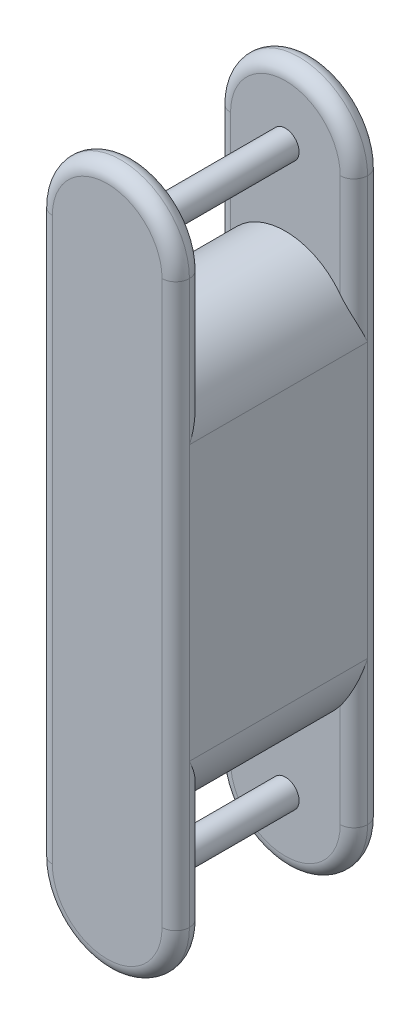
SolidWorks part; units mm, degrees
ref_plane "Front Plane" through (0, 0, 0) normal (0, 0, 1) x (1, 0, 0)
ref_plane "Top Plane" through (0, 0, 0) normal (0, 1, 0) x (1, 0, 0)
ref_plane "Right Plane" through (0, 0, 0) normal (1, 0, 0) x (0, 0, -1)
sketch "Sketch3" plane through (0, 0, 0) normal (0, 0, 1) x (1, 0, 0)
  line L0 (-50, -150) -> (-50, -205)
  line L1 (-50, 150) -> (50, 150)
  line L2 (-50, 150) -> (-50, -150)
  line L3 (-50, -150) -> (50, -150)
  line L4 (50, 150) -> (50, -150)
  line L5 (-50, 150) -> (50, -150) construction
  line L6 (-50, -150) -> (50, 150) construction
  line L7 (50, -150) -> (50, -205)
  line L8 (-50, 150) -> (-50, 205)
  line L9 (50, 150) -> (50, 205)
  arc A0 (-50, -205) -> (50, -205) centre (0, -205) ccw
  arc A1 (-50, 205) -> (50, 205) centre (0, 205) cw
  point P0 (0, 0)
  dimension "D1" = 300
  dimension "D2" = 100
  dimension "D3" = 55
  dimension "D4" = 55
  dimension "D5" = 55
  dimension "D6" = 55
extrude "Boss-Extrude1" add sketch "Sketch3" along normal mid plane 150 contours L4 L1 L2 L3 | L0 A0 L7 L3 | A1 L8 L1 L9 | L2 L1 L4 L3 region at (0, -197.7955, 0) region at (0, 0, 0) region at (0, 197.7955, 0)
sketch "Sketch4" plane through (0, 0, 0) normal (0, 1, 0) x (1, 0, 0)
  line L1 (-50, 55) -> (50, 55)
  line L2 (-50, 55) -> (-50, -55)
  line L3 (-50, -55) -> (50, -55)
  line L4 (50, 55) -> (50, -55)
  line L5 (-50, 55) -> (50, -55) construction
  line L6 (-50, -55) -> (50, 55) construction
  point P0 (0, 0)
  dimension "D1" = 100
  dimension "D2" = 110
extrude "Cut-Extrude1" cut sketch "Sketch4" against normal up to surface (55 mm away) from offset 150 up to face at (0, -230, 0) offset against normal yes
sketch "Sketch6" plane through (0, 0, 0) normal (0, 0, 1) x (1, 0, 0)
  arc A0 (-50, -205) -> (50, -205) centre (0, -205) ccw construction
  arc A1 (-50, -205) -> (50, -205) centre (0, -205) ccw
  circle A2 centre (0, -205) radius 10
  dimension "D1" = 20
extrude "Boss-Extrude2" add sketch "Sketch6" along normal mid plane 110 contours A2 region at (0, -205, 0)
extrude "Cut-Extrude2" cut sketch "Sketch4<2>" along normal up to surface (55 mm away) from offset 150 up to face at (0, 230, 0)
sketch "Sketch4<2>" plane through (0, 0, 0) normal (0, 1, 0) x (1, 0, 0) same geometry as "Sketch4"
mirror "Mirror2" about plane through (0, 0, 0) normal (0, 1, 0) of "Boss-Extrude2"
fillet "Fillet1" 2 edges at (50, 150, 0) (-50, 150, 0) type full round first side face at (50, 0, 0) second side face at (-50, 0, 0) middle face at (0, 150, 0)
fillet "Fillet2" 2 edges at (50, -150, 0) (-50, -150, 0) type full round first side face at (50, -8.3333, 0) second side face at (-50, -8.3333, 0) middle face at (0, -150, 0)
fillet "Fillet3" radius 10 20 edges at (-50, -152.5, 55) (0, -255, 55) (-50, -152.5, -55) (0, -255, -55) (-50, 152.5, 55) (0, 255, 55) (-50, 152.5, -55) (0, 255, -55) (0, 255, -75) (-50, 0, -75) (0, -255, -75) (50, 0, -75) (0, 255, 75) (50, 0, 75) (0, -255, 75) (-50, 0, 75) (50, -152.5, 55) (50, -152.5, -55) (50, 152.5, 55) (50, 152.5, -55)
